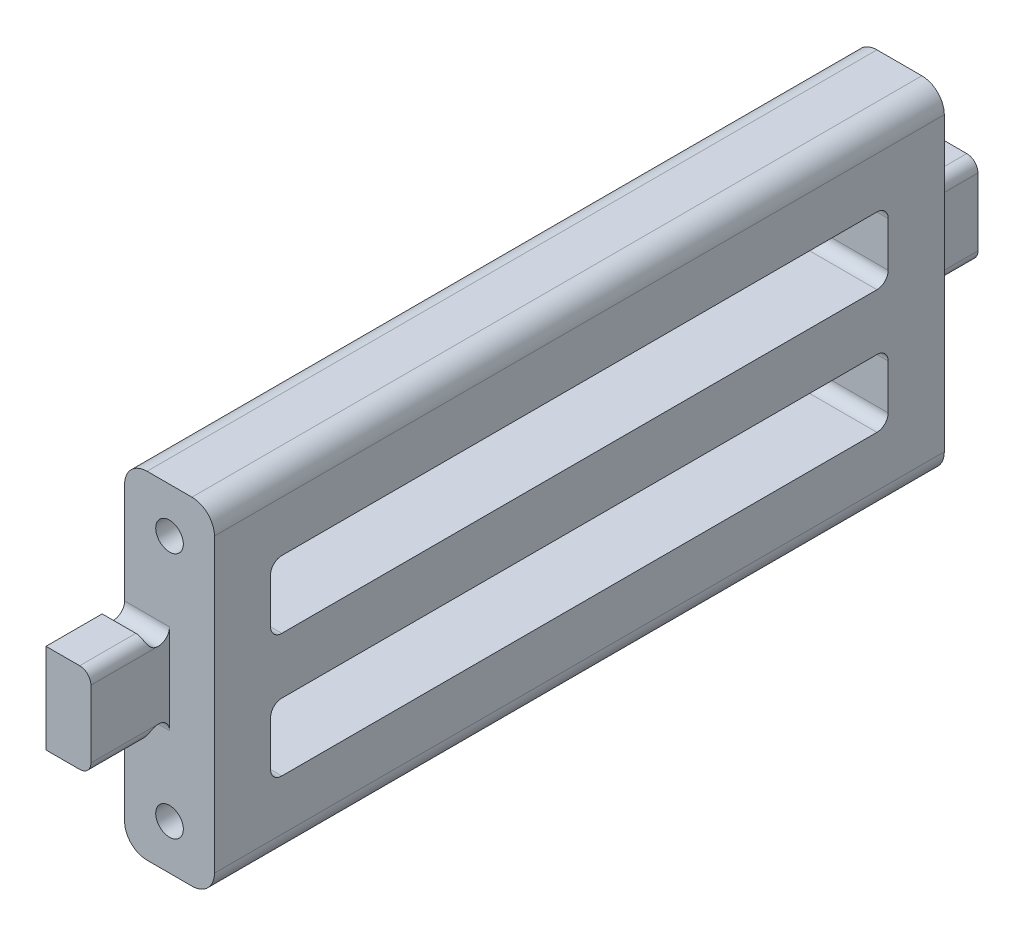
SolidWorks part; units mm, degrees
material "6061 Alloy"
ref_plane "Front Plane" through (0, 0, 0) normal (0, 0, 1) x (1, 0, 0)
ref_plane "Top Plane" through (0, 0, 0) normal (0, 1, 0) x (1, 0, 0)
ref_plane "Right Plane" through (0, 0, 0) normal (1, 0, 0) x (0, 0, -1)
sketch "Sketch1" plane through (0, 0, 0) normal (1, 0, 0) x (0, 0, -1)
  line L0 (0, 15) -> (0, -15) construction
  line L1 (-32.5, 15) -> (32.5, 15)
  line L2 (-32.5, 15) -> (-32.5, -15)
  line L3 (-32.5, -15) -> (32.5, -15)
  line L4 (32.5, 15) -> (32.5, -15)
  line L5 (-32.5, 15) -> (32.5, -15) construction
  line L6 (-32.5, -15) -> (32.5, 15) construction
  line L7 (39.5, -4) -> (34.5, -4)
  line L8 (-39.5, 4) -> (-34.5, 4)
  line L9 (-39.5, 4) -> (-39.5, -4)
  line L10 (-39.5, -4) -> (-34.5, -4)
  line L11 (-32.5, 4) -> (-32.5, -4)
  line L12 (39.5, 4) -> (39.5, -4)
  line L13 (39.5, 4) -> (34.5, 4)
  arc A0 (-34.5, 4) -> (-32.5, 4) centre (-33.5, 4) ccw
  arc A1 (-32.5, -4) -> (-34.5, -4) centre (-33.5, -4) ccw
  arc A2 (34.5, 4) -> (32.5, 4) centre (33.5, 4) cw
  arc A3 (32.5, -4) -> (34.5, -4) centre (33.5, -4) cw
  point P0 (0, 0)
  point P15 (0, 0)
  point P16 (0, 0)
  point P18 (-33.5, 4)
  point P19 (0, 0)
  dimension "D6" = 2
  dimension "D1" = 65
  dimension "D2" = 30
  dimension "D3" = 7
  dimension "D4" = 8
  dimension "D5" = 4
extrude "Boss-Extrude1" add sketch "Sketch1" along normal blind 8 contours L4 L1 L2 L3 region at (0, 0, 0)
extrude "Boss-Extrude3" add sketch "Sketch1<3>" along normal blind 4 contours A1 L2 A0 L8 L9 L10 | L4 A3 L7 L12 L13 A2 region at (0, 0, 36.1486) region at (0, 0, -36.1486)
sketch "Sketch1<3>" plane through (0, 0, 0) normal (1, 0, 0) x (0, 0, -1) same geometry as "Sketch1"
fillet "Fillet1" radius 2 4 edges at (0, 15, 0) (8, 15, 0) (8, -15, 0) (0, -15, 0)
sketch "Sketch2" plane through (0, 0, -32.5) normal (0, 0, -1) x (-1, 0, 0)
  line L2 (-6, 15) -> (-2, 15) construction
  line L4 (-8, 13) -> (-8, -13) construction
  circle A1 centre (-4, 11) radius 1.2295
  circle A2 centre (-4, -11) radius 1.2295
  point P6 (-3.38, 10.5131)
  dimension "D2" = 2.459
  dimension "D3" = 4
  dimension "D4" = 4
  dimension "D1" = 22
extrude "Cut-Extrude1" cut sketch "Sketch2" against normal blind 10
sketch "Sketch3" plane through (8, 0, 0) normal (1, 0, 0) x (0, 0, -1)
  line L1 (-27.5, 8.5) -> (27.5, 8.5)
  line L2 (-27.5, 8.5) -> (-27.5, 2.5)
  line L3 (-27.5, 2.5) -> (27.5, 2.5)
  line L4 (27.5, 8.5) -> (27.5, 2.5)
  line L12 (-27.5, -2.5) -> (27.5, -2.5)
  line L13 (27.5, -8.5) -> (27.5, -2.5)
  line L14 (-27.5, -8.5) -> (27.5, -8.5)
  line L15 (-27.5, -8.5) -> (-27.5, -2.5)
  point P8 (27.5, -1.9248)
  dimension "D1" = 55
  dimension "D2" = 8.5
  dimension "D3" = 55
  dimension "D4" = 27.5
  dimension "D5" = 2.5
  dimension "D6" = 8.5
  dimension "D7" = 2.5
  dimension "D8" = 27.5
extrude "Cut-Extrude2" cut sketch "Sketch3" against normal blind 10
fillet "Fillet3" radius 1 8 edges at (4, -8.5, -27.5) (4, -2.5, -27.5) (4, -8.5, 27.5) (4, -2.5, 27.5) (4, 2.5, -27.5) (4, 8.5, -27.5) (4, 2.5, 27.5) (4, 8.5, 27.5)
mirror "Mirror1" about plane through (0, 0, 0) normal (0, 0, 1) of "Cut-Extrude1"
fillet "Fillet6" radius 1 4 edges at (4, -4, 37) (4, 4, 37) (4, 4, -37) (4, -4, -37)
